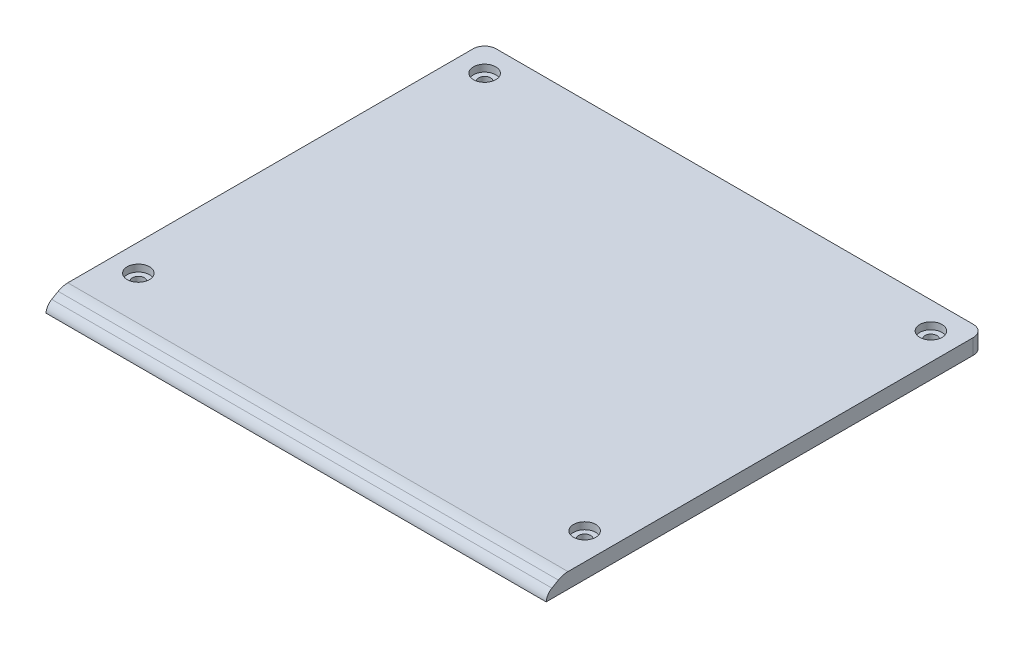
SolidWorks part; units mm, degrees
ref_plane "Спереди XY" through (0, 0, 0) normal (0, 0, 1) x (1, 0, 0)
ref_plane "Сверху XZ" through (0, 0, 0) normal (0, 1, 0) x (1, 0, 0)
ref_plane "Справа ZY" through (0, 0, 0) normal (1, 0, 0) x (0, 0, -1)
sketch "Эскиз1" plane through (0, 0, 0) normal (0, 1, 0) x (1, 0, 0)
  line L1 (-65, 57) -> (65, 57)
  line L2 (-65, 57) -> (-65, -57)
  line L3 (-65, -57) -> (65, -57)
  line L4 (65, 57) -> (65, -57)
  line L5 (-65, 57) -> (65, -57) construction
  line L6 (-65, -57) -> (65, 57) construction
  point P0 (0, 0)
  dimension "D1" = 130
  dimension "D2" = 114
extrude "Бобышка-Вытянуть1" add sketch "Эскиз1" along normal blind 4
chamfer "Фаска1" distance 2.5 angle 60 1 edges at (0, 4, 57) first distance on face at (0, 2, 57)
fillet "Скругление1" radius 5 1 edges at (0, 4, 52.6699)
fillet "Скругление2" radius 3 1 edges at (0, 1.5, 57)
fillet "Скругление3" radius 3 2 edges at (-65, 2, -57) (65, 2, -57)
sketch "Эскиз2" plane through (0, 4, 0) normal (0, 1, 0) x (1, 0, 0)
  line L0 (62, 57) -> (-62, 57) construction
  line L3 (-65, 54) -> (-65, -51.3301) construction
  circle A0 centre (-58, 50) radius 1.55
  point P6 (-65, 48.7773)
  point P7 (-65, 50.5764)
  dimension "D1" = 3.1
  dimension "D2" = 7
  dimension "D3" = 7
extrude "Вырез-Вытянуть1" cut sketch "Эскиз2" against normal through all
pattern_linear "Линейный массив1" count 2 spacing 116 along (1, 0, 0) count 2 spacing 90 along (0, 0, 1) of "Вырез-Вытянуть1"
sketch "Эскиз4" plane through (0, 4, 0) normal (0, 1, 0) x (1, 0, 0)
  circle A0 centre (-58, 50) radius 2.9
  dimension "D1" = 5.8
extrude "Вырез-Вытянуть2" cut sketch "Эскиз4" against normal blind 1.8
pattern_linear "Линейный массив2" count 2 spacing 116 along (1, 0, 0) count 2 spacing 90 along (0, 0, 1) of "Вырез-Вытянуть2"
